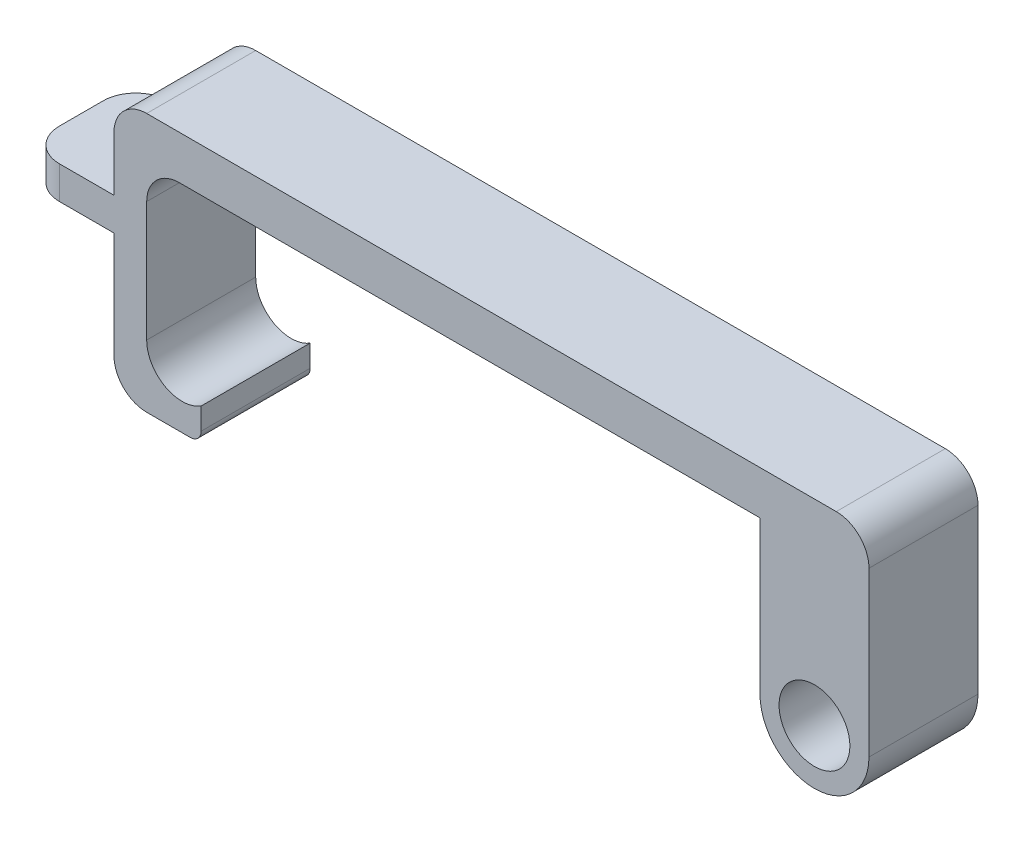
SolidWorks part; units mm, degrees
ref_plane "Plan de face" through (0, 0, 0) normal (0, 0, 1) x (1, 0, 0)
ref_plane "Plan de dessus" through (0, 0, 0) normal (0, 1, 0) x (1, 0, 0)
ref_plane "Plan de droite" through (0, 0, 0) normal (1, 0, 0) x (0, 0, -1)
sketch "Esquisse1" plane through (0, 0, 0) normal (0, 0, 1) x (1, 0, 0)
  line L0 (11.5884, 18.9102) -> (11.5884, -55.0898) construction
  line L1 (11.5884, 12.9102) -> (11.5884, 26.9102)
  line L2 (11.5884, 25.9102) -> (-36.4116, 25.9102) construction
  line L3 (11.5884, 26.9102) -> (-44.6616, 26.9102)
  line L4 (-44.6616, 26.9102) -> (-44.6616, 12.9102)
  line L5 (-47.6616, 22.9102) -> (-47.6616, 30.9102)
  line L6 (-39.6616, 10.1716) -> (-39.6616, 7.1716)
  line L7 (-39.6616, 7.1716) -> (-47.6616, 7.1716)
  line L8 (-47.6616, 7.1716) -> (-47.6616, 19.9102)
  line L9 (-47.6616, 30.9102) -> (21.5884, 30.9102)
  line L10 (21.5884, 30.9102) -> (21.5884, 12.9102)
  line L11 (-47.6616, 22.9102) -> (-55.6616, 22.9102)
  line L13 (-47.6616, 19.9102) -> (-55.6616, 19.9102)
  line L14 (-55.6616, 22.9102) -> (-55.6616, 19.9102)
  circle A0 centre (16.5884, 12.9102) radius 3.25
  arc A1 (11.5884, 12.9102) -> (21.5884, 12.9102) centre (16.5884, 12.9102) ccw
  circle A2 centre (-41.4116, 12.9102) radius 3.25 construction
  arc A3 (-44.6616, 12.9102) -> (-39.6616, 10.1716) centre (-41.4116, 12.9102) ccw
  dimension "D1" = 6.5
  dimension "D2" = 1
  dimension "D3" = 8
  dimension "D4" = 4
  dimension "D5" = 3
  dimension "D6" = 3
  dimension "D7" = 8
  dimension "D8" = 8
  dimension "D9" = 3
extrude "Boss.-Extru.1" add sketch "Esquisse1" along normal blind 10
fillet "Congé1" radius 3 6 edges at (-44.6616, 26.9102, 5) (-47.6616, 7.1716, 5) (21.5884, 30.9102, 5) (-47.6616, 30.9102, 5) (-55.6616, 21.4102, 10) (-55.6616, 21.4102, 0)
fillet "Congé2" radius 1 1 edges at (-39.6616, 7.1716, 5)
